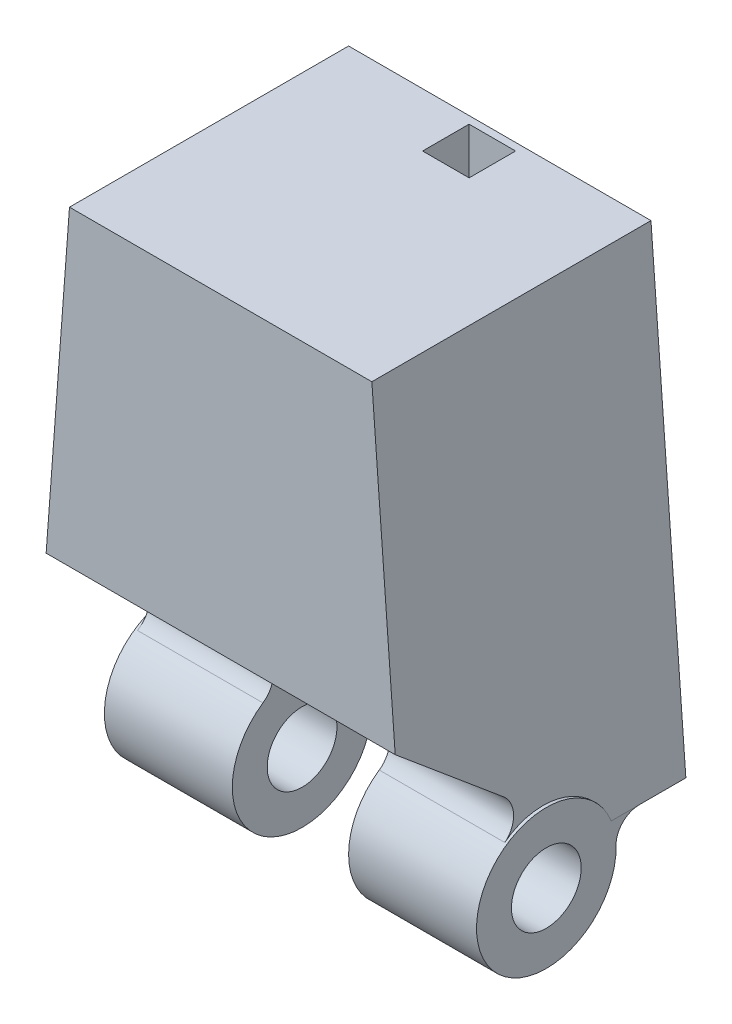
SolidWorks part; units mm, degrees
ref_plane "Front Plane" through (0, 0, 0) normal (0, 0, 1) x (1, 0, 0)
ref_plane "Top Plane" through (0, 0, 0) normal (0, 1, 0) x (1, 0, 0)
ref_plane "Right Plane" through (0, 0, 0) normal (1, 0, 0) x (0, 0, -1)
sketch "Sketch1" plane through (0, 0, 0) normal (0, 0, 1) x (1, 0, 0)
  line L1 (-8, -10) -> (8, -10)
  line L2 (-8, -10) -> (-6.5, 10)
  line L3 (8, -10) -> (6.5, 10)
  arc A0 (6.5, 10) -> (-6.5, 10) centre (0, 10) ccw
  point P4 (0, 0)
  point P9 (0, -10)
extrude "Boss-Extrude1" add sketch "Sketch1" along normal blind 12
sketch "Sketch3" plane through (0, 0, 0) normal (1, 0, 0) x (0, 0, -1)
  line L0 (0, -10) -> (-4, -10)
  line L1 (-12, -10) -> (0, -10) construction
  line L2 (-4, -10) -> (-12, -3.386)
  line L3 (-12, -10) -> (-12, 10) construction
  line L4 (-12, -3.386) -> (-12, -10)
  line L5 (-12, -10) -> (-4, -10)
extrude "Cut-Extrude1" cut sketch "Sketch3" against normal through all both and the other way through all contours L2 L4 L5
sketch "Sketch4" plane through (0, 0, 0) normal (1, 0, 0) x (0, 0, -1)
  line L0 (0, -10) -> (-6, -10)
  line L1 (-6, -10) -> (-6, -11.1)
  circle A0 centre (-6, -11.1) radius 1.5
  circle A1 centre (-6, -11.1) radius 3
extrude "Boss-Extrude2" add sketch "Sketch4" along normal mid plane 16 contours A1 A0 region at (0, -10.556, 3.1361)
sketch "Sketch5" plane through (0, 0, 0) normal (1, 0, 0) x (0, 0, -1)
  circle A0 centre (-6, -11.1) radius 1.5
  circle A1 centre (-6, -11.1) radius 3
extrude "Cut-Extrude2" cut sketch "Sketch5" against normal mid plane 5
fillet "Fillet1" radius 1 2 edges at (5.1792, -8.1133, 6.2821) (-5.1792, -8.1133, 6.2821)
fillet "Fillet2" radius 1 2 edges at (5.25, -10, 3.2089) (-5.25, -10, 3.2089)
sketch "Sketch6" plane through (0, 0, 0) normal (1, 0, 0) x (0, 0, -1)
  line L1 (-12, 16.5) -> (0, 16.5)
  line L2 (-12, 16.5) -> (-12, 10)
  line L3 (-12, 10) -> (0, 10)
  line L4 (0, 16.5) -> (0, 10)
extrude "Cut-Extrude3" cut sketch "Sketch6" against normal through all both and the other way through all
sketch "Sketch7" plane through (0, -7.9043, 6.5349) normal (0, -0.7707, 0.6372) x (1, 0, 0)
  line L0 (0, 7.091) -> (0, 5.891)
  line L1 (7.504, 7.091) -> (-7.504, 7.091) construction
  line L2 (0, 5.891) -> (5, 5.891)
  line L3 (5, 5.891) -> (5, 1.891)
  line L4 (5, 1.891) -> (-5, 1.891)
  line L5 (-5, 1.891) -> (-5, 5.891)
  line L6 (-5, 5.891) -> (0, 5.891)
extrude "Cut-Extrude4" cut sketch "Sketch7" against normal blind 5 contours L6 L5 L4 L3 L2 region at (0, -5.425, 9.5337)
sketch "Sketch8" plane through (-5, 0, 0) normal (1, 0, 0) x (0, 0, -1)
  circle A0 centre (-7.9408, -3.4982) radius 1.5
extrude "Boss-Extrude3" add sketch "Sketch8" along normal up to body separate body
sketch "Sketch9" plane through (0, 0, 0) normal (1, 0, 0) x (0, 0, -1)
  line L0 (-0.32, -10) -> (-2.32, -10)
  line L1 (-2.0013, -10) -> (0, -10) construction
  line L2 (-2.32, -10) -> (-2.32, 23.2129)
  line L3 (-2.32, 23.2129) -> (-0.32, 23.2129)
  line L4 (-0.32, 23.2129) -> (-0.32, -10)
extrude "Cut-Extrude5" cut sketch "Sketch9" against normal mid plane 2
